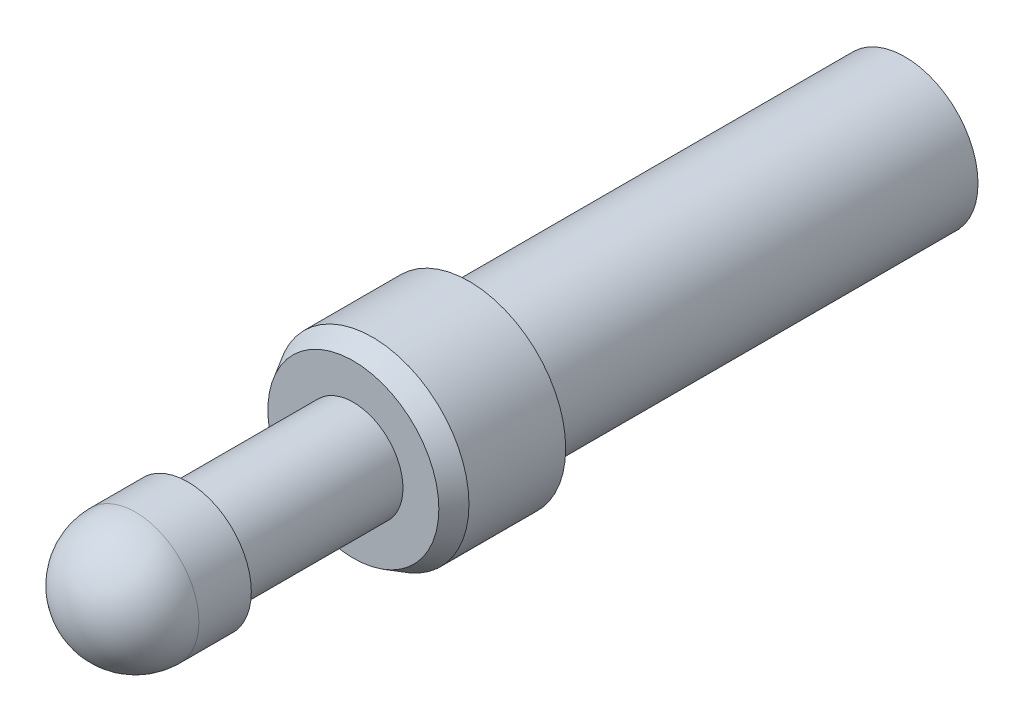
SolidWorks part; units mm, degrees
ref_plane "Face" through (0, 0, 0) normal (0, 0, 1) x (1, 0, 0)
ref_plane "Dessus" through (0, 0, 0) normal (0, 1, 0) x (1, 0, 0)
ref_plane "Droite" through (0, 0, 0) normal (1, 0, 0) x (0, 0, -1)
sketch "Esquisse1" plane through (0, 0, 0) normal (0, 0, 1) x (1, 0, 0)
  circle A0 centre (0, 0) radius 1.325
extrude "Extrusion1" add sketch "Esquisse1" along normal blind 7.9
sketch "Esquisse2" plane through (0, 0, 7.9) normal (0, 0, 1) x (1, 0, 0)
  circle A0 centre (0, 0) radius 1.75
extrude "Extrusion2" add sketch "Esquisse2" along normal blind 2.1
sketch "Esquisse3" plane through (0, 0, 10) normal (0, 0, 1) x (1, 0, 0)
  circle A0 centre (0, 0) radius 0.9
extrude "Extrusion3" add sketch "Esquisse3" along normal blind 3
sketch "Esquisse4" plane through (0, 0, 13) normal (0, 0, 1) x (1, 0, 0)
  circle A0 centre (0, 0) radius 1.15
extrude "Extrusion4" add sketch "Esquisse4" along normal blind 2.1
fillet "Congé1" radius 1.15 1 edges at (1.15, 0, 15.1)
chamfer "Chanfrein1" distance 0.2 angle 60 1 edges at (1.75, 0, 10) first distance on face at (1.75, 0, 10)
